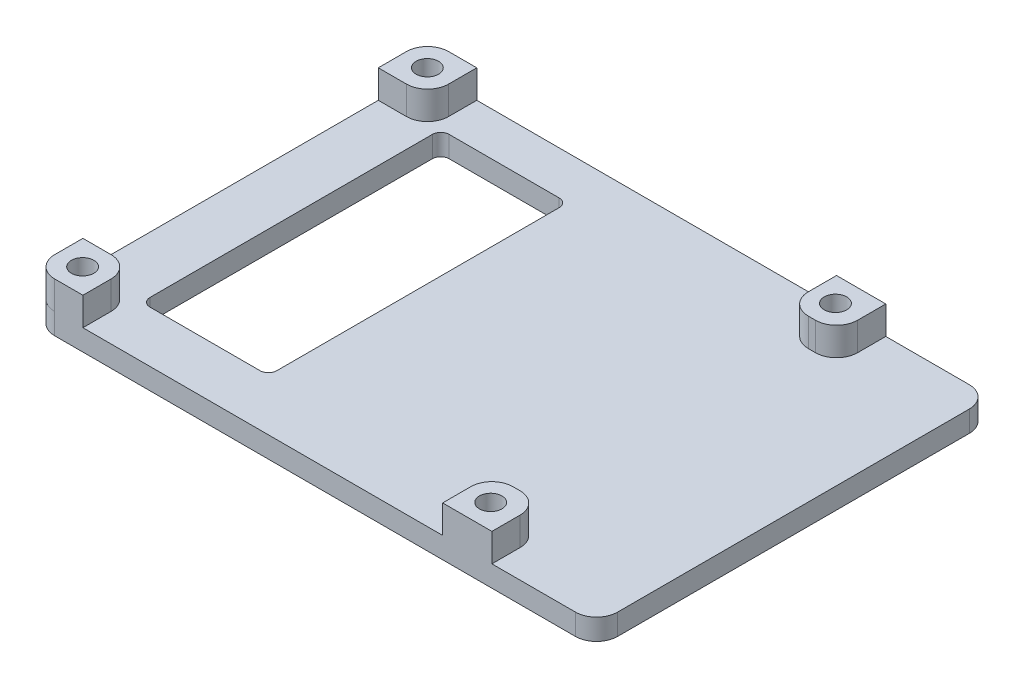
SolidWorks part; units mm, degrees
material "7075-T6 (SN)"
ref_plane "前视基准面" through (0, 0, 0) normal (0, 0, 1) x (1, 0, 0)
ref_plane "上视基准面" through (0, 0, 0) normal (0, 1, 0) x (1, 0, 0)
ref_plane "右视基准面" through (0, 0, 0) normal (1, 0, 0) x (0, 0, -1)
other "Configuration Table"
sketch "草图1" plane through (0, 0, 0) normal (0, 1, 0) x (1, 0, 0)
  line L0 (-70.9525, 18.3001) -> (-70.9986, 18.1669) construction
  line L5 (-80.009, 21.4027) -> (-0.009, 21.4027) construction
  line L6 (-0.009, 21.39) -> (-0.009, -28.5917)
  line L7 (-53.9406, -24.2884) -> (-53.9406, -23.4455) construction
  line L12 (-80.009, 21.4027) -> (-80.009, -28.6044)
  line L13 (-77.0217, -31.5917) -> (12.7873, -31.5917)
  line L14 (15.7746, -28.6044) -> (15.7746, 21.4027)
  line L15 (12.7873, 24.39) -> (-77.0217, 24.39)
  line L16 (-80.009, 21.4027) -> (-80.009, -28.6044)
  line L17 (-77.0217, -31.5917) -> (-3.009, -31.5917)
  line L19 (-3.009, 24.39) -> (-77.0217, 24.39)
  line L20 (-57.0741, 18.2303) -> (-57.0142, 16.884) construction
  line L21 (-57.0142, 16.884) -> (-53.9406, 15.8369) construction
  line L24 (-71.9124, -31.5917) -> (-71.9124, -38.4632) construction
  line L26 (-55.8106, -26.0508) -> (-55.3191, -21.9005) construction
  line L27 (-55.3191, -21.9005) -> (-52.2337, -21.9005) construction
  line L28 (-57.0741, 18.2303) -> (-53.9406, 18.2303) construction
  line L30 (-53.9406, 15.8369) -> (-53.9406, 18.2303) construction
  line L31 (-71.9686, 17.09) -> (-71.9659, 15.0188) construction
  line L32 (-54.4169, -24.2884) -> (-53.9406, -24.2884) construction
  line L33 (-70.9986, 18.1669) -> (-70.8339, 18.1567) construction
  line L34 (-70.8339, 18.1567) -> (-70.8158, 18.2696) construction
  line L35 (-70.8158, 18.2696) -> (-70.9525, 18.3001) construction
  line L36 (-70.8221, 18.2303) -> (-69.2002, 18.2303) construction
  line L38 (-70.7701, 18.2303) -> (-55.1406, 18.2303)
  line L39 (-71.9701, 17.0303) -> (-71.9701, -23.0884)
  line L40 (-70.7701, -24.2884) -> (-55.1406, -24.2884)
  line L41 (-53.9406, 17.0303) -> (-53.9406, -23.0884)
  arc A0 (-70.7701, 18.2303) -> (-71.9701, 17.0303) centre (-70.7701, 17.0303) ccw
  arc A1 (-53.9406, 17.0303) -> (-55.1406, 18.2303) centre (-55.1406, 17.0303) ccw
  arc A2 (-53.9406, -23.0884) -> (-55.1406, -24.2884) centre (-55.1406, -23.0884) cw
  arc A3 (-70.7701, -24.2884) -> (-71.9701, -23.0884) centre (-70.7701, -23.0884) cw
  circle A4 centre (-76.5285, 20.8867) radius 1.6
  circle A5 centre (-18.5286, 20.8866) radius 1.6
  circle A6 centre (-18.5283, -28.1137) radius 1.6
  circle A7 centre (-76.5283, -28.1135) radius 1.6
  arc A8 (-80.009, -28.6044) -> (-77.0217, -31.5917) centre (-77.0217, -28.6044) ccw
  arc A9 (12.7873, -31.5917) -> (15.7746, -28.6044) centre (12.7873, -28.6044) ccw
  arc A10 (15.7746, 21.4027) -> (12.7873, 24.39) centre (12.7873, 21.4027) ccw
  arc A11 (-77.0217, 24.39) -> (-80.009, 21.4027) centre (-77.0217, 21.4027) ccw
  arc A12 (-80.009, -28.6044) -> (-77.0217, -31.5917) centre (-77.0217, -28.6044) ccw
  arc A15 (-77.0217, 24.39) -> (-80.009, 21.4027) centre (-77.0217, 21.4027) ccw
  arc A19 (-0.009, 21.39) -> (-3.009, 24.39) centre (-3.009, 21.39) ccw
  arc A20 (-0.009, -28.5917) -> (-3.009, -31.5917) centre (-3.009, -28.5917) cw
  dimension "D2" = 3.2
  dimension "D3" = 3.2
  dimension "D4" = 3.2
  dimension "D5" = 3.2
  dimension "D6" = 3
  dimension "D7" = 1.2
  dimension "D8" = 1.2
  dimension "D9" = 1.2
  dimension "D10" = 1.2
  dimension "D11" = 3
  dimension "D1" = 0
extrude "凸台-拉伸1" add sketch "草图1" along normal blind 3
sketch "草图7" plane through (0, 3, 0) normal (0, 1, 0) x (1, 0, 0)
  line L0 (-80.009, 17.39) -> (-76.009, 17.39)
  line L1 (-77.009, 24.39) -> (-73.009, 24.39)
  line L2 (-80.009, 21.39) -> (-80.009, 17.39)
  line L3 (-77.009, -31.5917) -> (-73.009, -31.5917)
  line L5 (-80.009, -24.5917) -> (-76.009, -24.5917)
  line L6 (-73.009, 24.39) -> (-73.009, 20.39)
  line L7 (-21.8799, 24.39) -> (-21.8799, 20.39)
  line L8 (-14.8799, 24.39) -> (-14.8799, 20.39)
  line L9 (-18.8799, 17.39) -> (-17.8799, 17.39)
  line L10 (-73.009, -27.5917) -> (-73.009, -31.5917)
  line L11 (-18.8799, -24.5917) -> (-17.8799, -24.5917)
  line L12 (-21.8799, -27.5917) -> (-21.8799, -31.5917)
  line L13 (-14.8799, -27.5917) -> (-14.8799, -31.5917)
  line L14 (-80.009, -24.5917) -> (-80.009, -28.5917)
  line L15 (-21.8799, 24.39) -> (-14.8799, 24.39)
  line L16 (-21.8799, -31.5917) -> (-14.8799, -31.5917)
  arc A0 (-14.8799, -27.5917) -> (-17.8799, -24.5917) centre (-17.8799, -27.5917) ccw
  arc A1 (-18.8799, -24.5917) -> (-21.8799, -27.5917) centre (-18.8799, -27.5917) ccw
  arc A2 (-73.009, -27.5917) -> (-76.009, -24.5917) centre (-76.009, -27.5917) ccw
  arc A3 (-18.8799, 17.39) -> (-21.8799, 20.39) centre (-18.8799, 20.39) cw
  arc A4 (-76.009, 17.39) -> (-73.009, 20.39) centre (-76.009, 20.39) ccw
  arc A5 (-14.8799, 20.39) -> (-17.8799, 17.39) centre (-17.8799, 20.39) cw
  arc A7 (-80.009, -28.5917) -> (-77.009, -31.5917) centre (-77.009, -28.5917) ccw
  arc A9 (-77.009, 24.39) -> (-80.009, 21.39) centre (-77.009, 21.39) ccw
  circle A10 centre (-76.5283, -28.1135) radius 1.6 construction
  circle A11 centre (-18.5283, -28.1137) radius 1.6 construction
  circle A12 centre (-18.5286, 20.8866) radius 1.6 construction
  circle A13 centre (-76.5285, 20.8867) radius 1.6 construction
  circle A14 centre (-76.5283, -28.1135) radius 1.6
  circle A15 centre (-18.5283, -28.1137) radius 1.6
  circle A16 centre (-18.5286, 20.8866) radius 1.6
  circle A17 centre (-76.5285, 20.8867) radius 1.6
  point P22 (-21.8799, -24.5917)
  dimension "D5" = 3
  dimension "D1" = 7
  dimension "D2" = 7
  dimension "D3" = 7
  dimension "D4" = 7
extrude "凸台-拉伸2" add sketch "草图7" along normal blind 4
